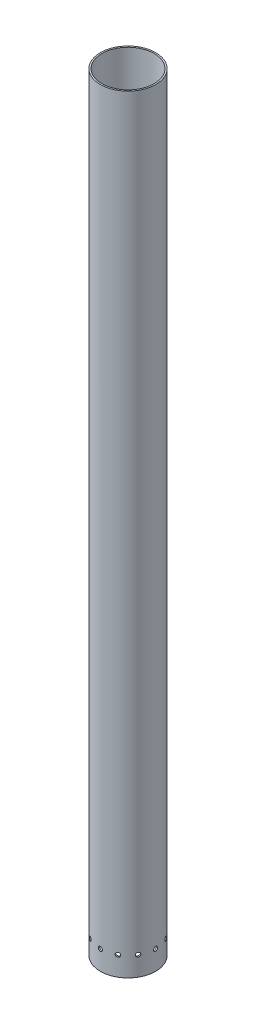
SolidWorks part; units mm, degrees
material "6063-T6"
ref_plane "Front Plane" through (0, 0, 0) normal (0, 0, 1) x (1, 0, 0)
ref_plane "Top Plane" through (0, 0, 0) normal (0, 1, 0) x (1, 0, 0)
ref_plane "Right Plane" through (0, 0, 0) normal (1, 0, 0) x (0, 0, -1)
sketch "Sketch1" plane through (0, 0, 0) normal (0, 0, 1) x (1, 0, 0)
  line L0 (0, 0) -> (0, 45.6531) construction
  line L1 (25.5143, 17.2858) -> (26.9875, 17.2858)
  line L2 (25.5143, 17.2858) -> (25.5143, -732.0142)
  line L3 (25.5143, -732.0142) -> (26.9875, -732.0142)
  line L4 (26.9875, 17.2858) -> (26.9875, -732.0142)
revolve "Revolve1" add sketch "Sketch1" angle 360 about L0
ref_plane "Plane1" through (0, 0, -26.9875) normal (0, 0, -1) x (-1, 0, 0)
sketch "Sketch2" plane through (0, 0, -26.9875) normal (0, 0, -1) x (-1, 0, 0)
  point P0 (0, -712.9642)
hole_wizard "#10-32 Tapped Hole1" positions "Sketch2" profile "Sketch3" tap size "#10-32" standard "ANSI Inch"
sketch "Sketch3" plane through (0, -712.9642, -26.9875) normal (1, 0, 0) x (0, 1, 0)
  line L0 (0, 0) -> (0, 15.1833)
  line L1 (0, 15.1833) -> (2.0193, 13.97)
  line L2 (2.0193, 13.97) -> (2.0193, 0)
  line L5 (2.0193, 0) -> (0, 0)
  line L10 (0, 15.1833) -> (-2.0193, 13.97) construction
  line L11 (0, -6.35) -> (0, 107.95) construction
  dimension "Tap Drill Dia." = 4.0386
  dimension "Tap Drill Depth" = 13.97
  dimension "Drill Angle" = 118
pattern_circular "CirPattern1" count 12 over 360 about axis through (0, 0, 0) along (0, -1, 0) of "#10-32 Tapped Hole1" reverse direction yes
